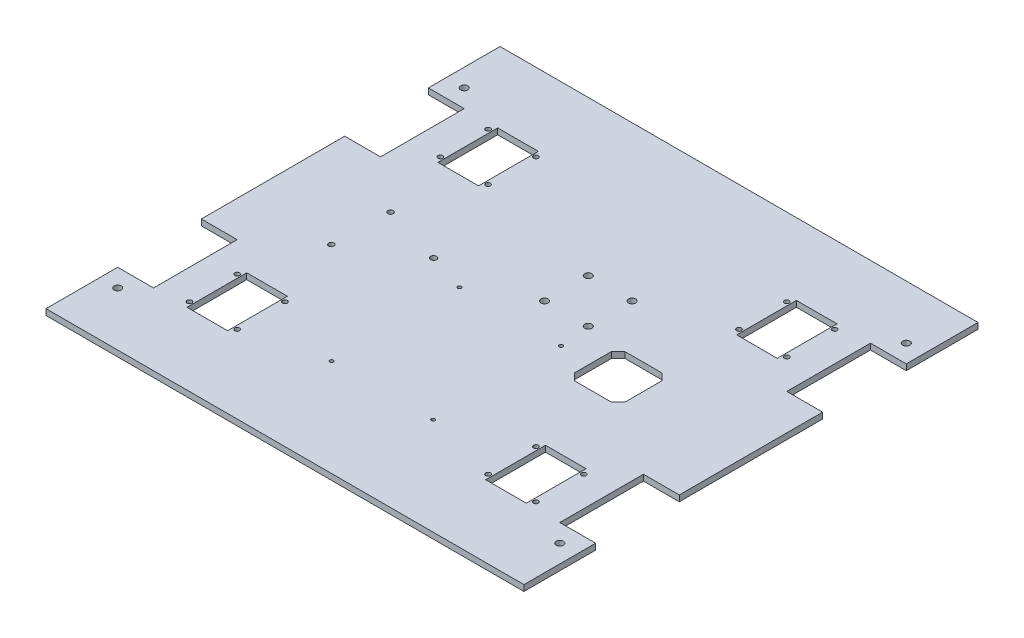
SolidWorks part; units mm, degrees
ref_plane "前基準面" through (0, 0, 0) normal (0, 0, 1) x (1, 0, 0)
ref_plane "上基準面" through (0, 0, 0) normal (0, 1, 0) x (1, 0, 0)
ref_plane "右基準面" through (0, 0, 0) normal (1, 0, 0) x (0, 0, -1)
sketch "草圖1" plane through (0, 0, 0) normal (0, 1, 0) x (1, 0, 0)
  line L0 (200, 190) -> (200, -190)
  line L1 (200, 190) -> (-200, 190)
  line L3 (200, -190) -> (-200, -190)
  line L4 (-200, 190) -> (-200, -190)
  line L5 (0, -190) -> (0, 190) construction
  line L6 (200, 0) -> (-200, 0) construction
  line L8 (-200, 130) -> (-200, -130) construction
  line L10 (-170, 130) -> (-170, -130) construction
  line L11 (-200, 130) -> (200, 130) construction
  line L12 (-200, 130) -> (-200, 190) construction
  line L13 (-200, 190) -> (200, 190) construction
  line L15 (-200, -130) -> (200, -130) construction
  line L16 (-200, -130) -> (-200, -190) construction
  line L17 (-200, -190) -> (200, -190) construction
  line L19 (170, 130) -> (170, -130) construction
  point P0 (0, 0)
  dimension "D1" = 400
  dimension "D2" = 260
  dimension "D3" = 60
  dimension "D4" = 60
  dimension "D5" = 30
extrude "填料-伸長1" add sketch "草圖1" along normal blind 5
sketch "草圖2" plane through (0, 5, 0) normal (0, 1, 0) x (1, 0, 0)
  line L0 (200, -190) -> (200, 190) construction
  line L1 (-200, 190) -> (200, 190) construction
  line L5 (-185, 190) -> (-185, -190) construction
  line L21 (-200, 190) -> (200, 190) construction
  line L22 (-200, 190) -> (-200, 130) construction
  line L23 (-200, 130) -> (200, 130) construction
  line L24 (-275.3304, 0) -> (275.3304, 0) construction
  line L25 (0, 247.3454) -> (0, -229.8147) construction
  line L42 (200, 190) -> (200, 130) construction
  line L44 (-155, 35) -> (-72.5, 35) construction
  line L45 (-155, 35) -> (-155, -35) construction
  line L46 (-155, -35) -> (-72.5, -35) construction
  line L47 (-72.5, 35) -> (-72.5, -35) construction
  line L59 (-200, 160) -> (200, 160) construction
  line L60 (-200, 145) -> (200, 145) construction
  line L61 (-200, -145) -> (200, -145) construction
  line L62 (-200, -160) -> (200, -160) construction
  line L63 (-200, -130) -> (200, -130) construction
  line L64 (200, -190) -> (200, -130) construction
  line L65 (-200, -190) -> (200, -190) construction
  line L66 (-200, -190) -> (-200, -130) construction
  line L67 (185, -190) -> (185, 190) construction
  line L68 (-200, 130) -> (-170, 130) construction
  line L69 (-200, 130) -> (-200, -130) construction
  line L70 (-200, -130) -> (-170, -130) construction
  line L71 (-170, 130) -> (-170, -130) construction
  line L72 (200, 130) -> (170, 130) construction
  line L73 (200, 130) -> (200, -130) construction
  line L74 (200, -130) -> (170, -130) construction
  line L75 (170, 130) -> (170, -130) construction
  line L76 (170, -60) -> (200, -60)
  line L77 (-200, 130) -> (-170, 130)
  line L78 (-200, 130) -> (-200, 60)
  line L79 (-200, 60) -> (-170, 60)
  line L80 (-170, 130) -> (-170, 60)
  line L81 (-170, -130) -> (-200, -130)
  line L82 (-170, -130) -> (-170, -60)
  line L83 (-170, -60) -> (-200, -60)
  line L84 (-200, -130) -> (-200, -60)
  line L85 (200, -130) -> (200, -60)
  line L86 (170, -130) -> (200, -130)
  line L87 (170, -130) -> (170, -60)
  line L88 (200, 60) -> (170, 60)
  line L89 (170, 130) -> (170, 60)
  line L90 (200, 130) -> (170, 130)
  line L91 (200, 130) -> (200, 60)
  line L100 (100, -80) -> (150, -80) construction
  line L101 (0, 63.85) -> (42.7, 63.85) construction
  line L102 (0, 63.85) -> (0, 21.15) construction
  line L103 (0, 21.15) -> (42.7, 21.15) construction
  line L104 (42.7, 63.85) -> (42.7, 21.15) construction
  line L105 (-150, -80) -> (-100, -80) construction
  line L106 (-150, -80) -> (-150, -130) construction
  line L107 (-150, -130) -> (-100, -130) construction
  line L108 (-100, -80) -> (-100, -130) construction
  line L109 (-142, -80) -> (-108, -80)
  line L110 (-142, -80) -> (-142, -130)
  line L111 (-142, -130) -> (-108, -130)
  line L112 (-108, -80) -> (-108, -130)
  line L113 (100, -80) -> (100, -130) construction
  line L114 (100, -130) -> (150, -130) construction
  line L115 (150, -80) -> (150, -130) construction
  line L116 (108, -80) -> (142, -80)
  line L117 (108, -80) -> (108, -130)
  line L118 (108, -130) -> (142, -130)
  line L119 (142, -80) -> (142, -130)
  line L120 (-150, 130) -> (-100, 130) construction
  line L121 (-150, 130) -> (-150, 80) construction
  line L122 (-150, 80) -> (-100, 80) construction
  line L123 (-100, 130) -> (-100, 80) construction
  line L124 (-142, 130) -> (-108, 130)
  line L125 (-142, 130) -> (-142, 80)
  line L126 (-142, 80) -> (-108, 80)
  line L127 (-108, 130) -> (-108, 80)
  line L128 (100, 130) -> (150, 130) construction
  line L129 (100, 130) -> (100, 80) construction
  line L130 (100, 80) -> (150, 80) construction
  line L131 (150, 130) -> (150, 80) construction
  line L132 (108, 130) -> (142, 130)
  line L133 (108, 130) -> (108, 80)
  line L134 (108, 80) -> (142, 80)
  line L135 (142, 130) -> (142, 80)
  line L136 (67.7, 15.5) -> (73.35, 21.15)
  line L137 (44, -110) -> (-44, -110) construction
  line L138 (44, -110) -> (44, 0) construction
  line L139 (44, 0) -> (-44, 0) construction
  line L140 (-44, -110) -> (-44, 0) construction
  line L141 (73.35, 21.15) -> (104.35, 21.15)
  line L142 (67.7, 15.5) -> (67.7, -15.5)
  line L143 (73.35, -21.15) -> (104.35, -21.15)
  line L144 (110, 15.5) -> (110, -15.5)
  line L145 (104.35, 21.15) -> (110, 15.5)
  line L146 (104.35, -21.15) -> (110, -15.5)
  line L147 (67.7, -15.5) -> (73.35, -21.15)
  circle A21 centre (-127.07, -24.13) radius 2.25
  circle A22 centre (-125.8, 24.13) radius 2.25
  circle A23 centre (-74.5, 8.89) radius 2.5
  circle A32 centre (-185, 145) radius 3
  circle A33 centre (185, 145) radius 3
  circle A34 centre (-185, -145) radius 3
  circle A35 centre (185, -145) radius 3
  circle A40 centre (3, 60.85) radius 3
  circle A41 centre (39.7, 60.85) radius 3
  circle A42 centre (3, 24.15) radius 3
  circle A43 centre (39.7, 24.15) radius 3
  circle A44 centre (-145, -85) radius 2
  circle A45 centre (-105, -85) radius 2
  circle A46 centre (-145, -125) radius 2
  circle A47 centre (-105, -125) radius 2
  circle A48 centre (105, -85) radius 2
  circle A49 centre (145, -85) radius 2
  circle A50 centre (105, -125) radius 2
  circle A51 centre (145, -125) radius 2
  circle A52 centre (-145, 125) radius 2
  circle A53 centre (-105, 125) radius 2
  circle A54 centre (-145, 85) radius 2
  circle A55 centre (-105, 85) radius 2
  circle A56 centre (105, 125) radius 2
  circle A57 centre (145, 125) radius 2
  circle A58 centre (105, 85) radius 2
  circle A59 centre (145, 85) radius 2
  circle A60 centre (-42.5, -1.5) radius 1.5
  circle A61 centre (42.5, -1.5) radius 1.5
  circle A62 centre (-42.5, -108.5) radius 1.5
  circle A63 centre (42.5, -108.5) radius 1.5
  circle A64 centre (73.35, 15.5) radius 1.5 construction
  circle A65 centre (104.35, 15.5) radius 1.5 construction
  circle A66 centre (73.35, -15.5) radius 1.5 construction
  circle A67 centre (104.35, -15.5) radius 1.5 construction
  point P54 (88.85, 0)
  point P55 (88.85, 21.15)
  point P56 (0, 0)
  point P57 (120.319, 230.9396)
  point P62 (-113.75, 0)
  point P64 (-155, 0)
  point P66 (131.1121, 0)
  point P67 (136.3283, 0)
  point P68 (0, 0)
  point P69 (42.7648, 60)
  point P70 (114.7044, 0)
  point P71 (21.35, 71.9472)
  point P72 (87.9188, 0)
  point P102 (-113.75, 35)
  point P175 (0, 0)
  point P177 (-44, -55)
  point P182 (0, -55)
  point P183 (21.35, 63.85)
  point P185 (0, 42.5)
  point P191 (21.35, 42.5)
  point P204 (67.7, 21.15)
  point P205 (110, -21.15)
  point P206 (67.7, -21.15)
  point P207 (110, 21.15)
  point P223 (88.85, -21.15)
  point P224 (67.7, 0)
  dimension "D5" = 60
  dimension "D6" = 15
  dimension "D7" = 30
  dimension "D9" = 6
  dimension "D18" = 4.5
  dimension "D25" = 5
  dimension "D28" = 42.7
  dimension "D10" = 6
  dimension "D30" = 6
  dimension "D31" = 50
  dimension "D32" = 50
  dimension "D33" = 40
  dimension "D37" = 4
  dimension "D46" = 4
  dimension "D55" = 4
  dimension "D64" = 4
  dimension "D73" = 3
  dimension "D77" = 3
  dimension "D3" = 15
  dimension "D4" = 15
  dimension "D11" = 70
  dimension "D12" = 90
  dimension "D16" = 82.5
  dimension "D17" = 70
  dimension "D19" = 10.87
  dimension "D20" = 27.93
  dimension "D21" = 29.2
  dimension "D22" = 10.87
  dimension "D23" = 26.11
  dimension "D24" = 2
  dimension "D29" = 42.7
  dimension "D36" = 40
  dimension "D38" = 5
  dimension "D39" = 5
  dimension "D40" = 34
  dimension "D41" = 8
  dimension "D42" = 50
  dimension "D43" = 50
  dimension "D44" = 40
  dimension "D45" = 40
  dimension "D47" = 5
  dimension "D48" = 5
  dimension "D49" = 34
  dimension "D50" = 8
  dimension "D51" = 50
  dimension "D52" = 50
  dimension "D53" = 40
  dimension "D54" = 40
  dimension "D56" = 5
  dimension "D57" = 5
  dimension "D58" = 34
  dimension "D59" = 8
  dimension "D60" = 50
  dimension "D61" = 50
  dimension "D62" = 40
  dimension "D63" = 40
  dimension "D65" = 5
  dimension "D66" = 5
  dimension "D67" = 34
  dimension "D68" = 8
  dimension "D69" = 20
  dimension "D70" = 20
  dimension "D71" = 88
  dimension "D72" = 110
  dimension "D74" = 15
  dimension "D75" = 42.3
  dimension "D76" = 42.3
  dimension "D78" = 31
  dimension "D79" = 31
  dimension "D80" = 5.65
  dimension "D81" = 5.65
  dimension "D82" = 5.65
  dimension "D83" = 5.65
  dimension "D84" = 5.65
  dimension "D85" = 5.65
  dimension "D86" = 5.65
  dimension "D87" = 5.65
  dimension "D88" = 5.65
  dimension "D89" = 5.65
extrude "除料-伸長1" cut sketch "草圖2" against normal through all
